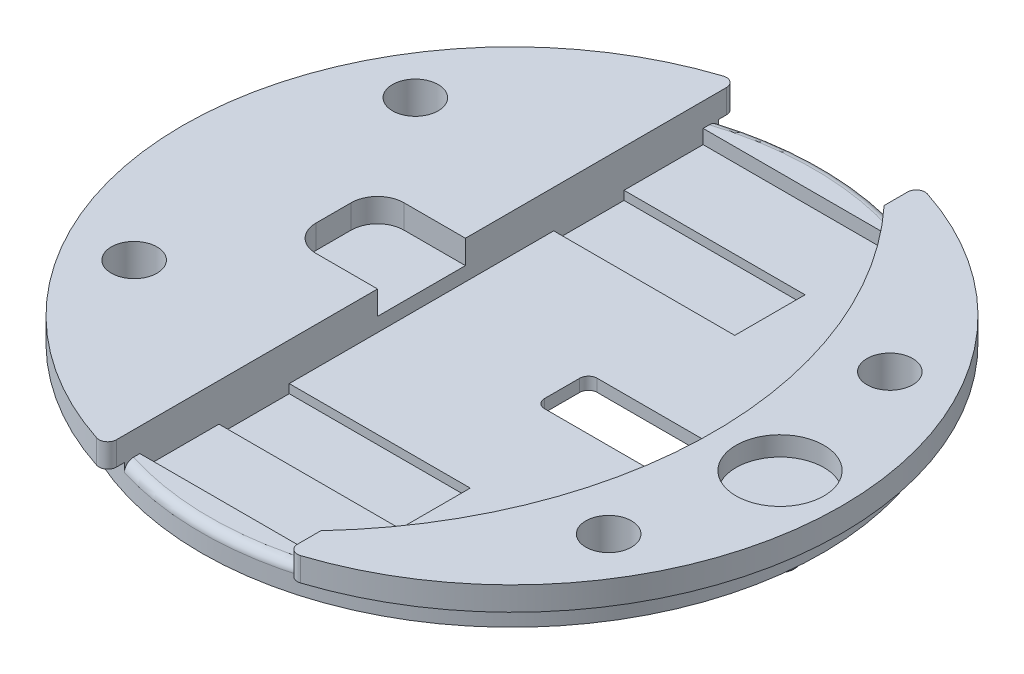
SolidWorks part; units mm, degrees
ref_plane "Front Plane" through (0, 0, 0) normal (0, 0, 1) x (1, 0, 0)
ref_plane "Top Plane" through (0, 0, 0) normal (0, 1, 0) x (1, 0, 0)
ref_plane "Right Plane" through (0, 0, 0) normal (1, 0, 0) x (0, 0, -1)
sketch "Sketch1" plane through (0, 0, 0) normal (0, 1, 0) x (1, 0, 0)
  line L1 (5.7, 3) -> (19.7, 3)
  line L2 (5.7, 3) -> (5.7, -3)
  line L3 (5.7, -3) -> (19.7, -3)
  line L4 (19.7, 3) -> (19.7, -3)
  line L5 (6.35, 2.54) -> (19.05, 2.54) construction
  line L6 (6.35, 2.54) -> (6.35, -2.54) construction
  line L7 (6.35, -2.54) -> (19.05, -2.54) construction
  line L8 (19.05, 2.54) -> (19.05, -2.54) construction
  line L9 (-27, 16) -> (27, 16) construction
  line L10 (-27, 16) -> (-27, -16) construction
  line L11 (-27, -16) -> (27, -16) construction
  line L12 (27, 16) -> (27, -16) construction
  circle A0 centre (0, 0) radius 35.35
  circle A1 centre (27, 16) radius 2.6
  circle A2 centre (-27, 16) radius 2.6
  circle A3 centre (-27, -16) radius 2.6
  circle A4 centre (27, -16) radius 2.6
  point P7 (5.7, 0)
  point P12 (12.7, -2.54)
  point P13 (12.7, -3)
  point P14 (6.35, 0)
  point P27 (0, 16)
  point P28 (27, 0)
  dimension "D1" = 70.7
  dimension "D7" = 5.2
  dimension "D8" = 5.2
  dimension "D9" = 5.2
  dimension "D10" = 5.2
  dimension "D2" = 6
  dimension "D3" = 14
  dimension "D4" = 5.08
  dimension "D5" = 12.7
  dimension "D6" = 6.35
  dimension "D11" = 54
  dimension "D12" = 32
extrude "Boss-Extrude1" add sketch "Sketch1" along normal blind 1.4
fillet "Fillet1" radius 1 4 edges at (5.7, 0.7, -3) (5.7, 0.7, 3) (19.7, 0.7, 3) (19.7, 0.7, -3)
sketch "Sketch3" plane through (0, 1.4, 0) normal (0, 1, 0) x (1, 0, 0)
  line L1 (-10.3, 32.05) -> (10.3, 32.05)
  line L2 (-10.3, 32.05) -> (-10.3, -32.05)
  line L3 (-10.3, -32.05) -> (10.3, -32.05)
  circle A0 centre (27, 16) radius 2.6 construction
  circle A1 centre (27, -16) radius 2.6 construction
  circle A2 centre (-27, -16) radius 2.6 construction
  circle A3 centre (-27, 16) radius 2.6 construction
  circle A4 centre (0, 0) radius 35.35 construction
  circle A5 centre (27, 16) radius 2.6
  circle A6 centre (27, -16) radius 2.6
  circle A7 centre (-27, -16) radius 2.6
  circle A8 centre (-27, 16) radius 2.6
  circle A9 centre (0, 0) radius 35.35
  arc A10 (10.3, -32.05) -> (10.3, 32.05) centre (-24.0773, 0) ccw
  point P20 (0, 32.05)
  point P23 (-10.3, 0)
  dimension "D3" = 47
  dimension "D1" = 20.6
  dimension "D2" = 64.1
extrude "Boss-Extrude3" add sketch "Sketch3" along normal blind 1.6
sketch "Sketch4" plane through (0, 3, 0) normal (0, 1, 0) x (1, 0, 0)
  line L0 (-10.3, 36.0577) -> (-10.3, 5)
  line L1 (-10.3, 32.05) -> (-10.3, -32.05) construction
  line L2 (10.3, 32.05) -> (10.3, 36.0577)
  line L3 (10.3, -32.05) -> (10.3, -36.0577)
  line L4 (-10.3, -5) -> (-10.3, -36.0577)
  line L5 (-10.3, -5) -> (-20.3, -5)
  line L7 (-10.3, 5) -> (-20.3, 5)
  line L8 (-20.3, -5) -> (-20.3, 5)
  arc A0 (10.3, -32.05) -> (10.3, 32.05) centre (-24.0773, 0) ccw construction
  arc A1 (10.3, -36.0577) -> (10.3, 36.0577) centre (0, 0) ccw
  arc A3 (10.3, -32.05) -> (10.3, 32.05) centre (-24.0773, 0) ccw
  circle A4 centre (-27, 16) radius 2.6 construction
  circle A5 centre (-27, -16) radius 2.6 construction
  circle A6 centre (27, -16) radius 2.6 construction
  circle A7 centre (27, 16) radius 2.6 construction
  circle A8 centre (-27, 16) radius 2.6
  circle A9 centre (-27, -16) radius 2.6
  circle A10 centre (27, -16) radius 2.6
  circle A11 centre (27, 16) radius 2.6
  arc A12 (-10.3, 36.0577) -> (-10.3, -36.0577) centre (0, 0) ccw
  point P27 (-20.3, 0)
  dimension "D1" = 75
  dimension "D2" = 10
  dimension "D3" = 10
extrude "Boss-Extrude4" add sketch "Sketch4" along normal blind 2.7
sketch "Sketch5" plane through (0, 5.7, 0) normal (0, 1, 0) x (1, 0, 0)
  circle A0 centre (30.5, 0) radius 5
  dimension "D2" = 10
  dimension "D1" = 30.5
extrude "Cut-Extrude1" cut sketch "Sketch5" against normal blind 2.2
sketch "Sketch7" plane through (0, 1.4, 0) normal (0, 1, 0) x (1, 0, 0)
  line L0 (-10.3, 32.05) -> (-10.3, -32.05) construction
  line L1 (-10.3, -23.05) -> (10.3, -23.05)
  line L2 (-10.3, -23.05) -> (-10.3, -15.05)
  line L3 (-10.3, -15.05) -> (10.3, -15.05)
  line L4 (10.3, -23.05) -> (10.3, -15.05)
  line L5 (-10.3, -36.0577) -> (-10.3, -5) construction
  line L6 (-10.3, 15.05) -> (10.3, 15.05)
  line L7 (-10.3, 15.05) -> (-10.3, 23.05)
  line L8 (-10.3, 23.05) -> (10.3, 23.05)
  line L9 (10.3, 15.05) -> (10.3, 23.05)
  line L10 (10.3, 36.0577) -> (10.3, 32.05) construction
  line L11 (10.3, -32.05) -> (10.3, -36.0577) construction
  line L12 (10.3, 32.05) -> (-10.3, 32.05) construction
  line L13 (-10.3, -32.05) -> (10.3, -32.05) construction
  dimension "D1" = 8
  dimension "D2" = 8
  dimension "D3" = 9
  dimension "D4" = 9
extrude "Cut-Extrude3" cut sketch "Sketch7" against normal blind 1
sketch "Sketch8" plane through (0, 0, 0) normal (0, -1, 0) x (1, 0, 0)
  circle A0 centre (30.5, 0) radius 1.9
  dimension "D2" = 3.8
  dimension "D1" = 30.5
extrude "Boss-Extrude6" add sketch "Sketch8" along normal blind 3.5
fillet "Fillet2" radius 1 7 edges at (10.3, 4.35, 36.0577) (0, 3, 35.35) (-10.3, 4.35, 36.0577) (-10.3, 4.35, -36.0577) (0, 3, -35.35) (10.3, 4.35, -36.0577) (30.5, -3.5, -1.9)
sketch "Sketch9" plane through (0, 3, 0) normal (0, -1, 0) x (1, 0, 0)
  line L0 (-10.3, -34.7068) -> (-10.3, -33.8162) construction
  line L1 (-10.3, 33.8162) -> (-10.3, 34.7068) construction
  line L2 (10.3, -33.8162) -> (10.3, -34.7068) construction
  line L3 (10.3, 34.7068) -> (10.3, 33.8162) construction
  line L4 (-10.3, -34.7068) -> (-10.3, -33.8162)
  line L5 (-10.3, 33.8162) -> (-10.3, 34.7068)
  line L6 (10.3, -33.8162) -> (10.3, -34.7068)
  line L7 (10.3, 34.7068) -> (10.3, 33.8162)
  arc A0 (-11.6096, 35.6576) -> (-11.6096, -35.6576) centre (0, 0) ccw construction
  arc A1 (-11.6096, -35.6576) -> (-10.3, -34.7068) centre (-11.3, -34.7068) ccw construction
  arc A2 (-10.3, 33.8162) -> (-10.3, -33.8162) centre (0, 0) ccw construction
  arc A3 (-10.3, 34.7068) -> (-11.6096, 35.6576) centre (-11.3, 34.7068) ccw construction
  arc A4 (10.3, -34.7068) -> (11.6096, -35.6576) centre (11.3, -34.7068) ccw construction
  arc A5 (11.6096, -35.6576) -> (11.6096, 35.6576) centre (0, 0) ccw construction
  arc A6 (11.6096, 35.6576) -> (10.3, 34.7068) centre (11.3, 34.7068) ccw construction
  arc A7 (10.3, -33.8162) -> (10.3, 33.8162) centre (0, 0) ccw construction
  arc A8 (-11.6096, 35.6576) -> (-11.6096, -35.6576) centre (0, 0) ccw
  arc A9 (-11.6096, -35.6576) -> (-10.3, -34.7068) centre (-11.3, -34.7068) ccw
  arc A10 (-10.3, 33.8162) -> (-10.3, -33.8162) centre (0, 0) ccw
  arc A11 (-10.3, 34.7068) -> (-11.6096, 35.6576) centre (-11.3, 34.7068) ccw
  arc A12 (10.3, -34.7068) -> (11.6096, -35.6576) centre (11.3, -34.7068) ccw
  arc A13 (11.6096, -35.6576) -> (11.6096, 35.6576) centre (0, 0) ccw
  arc A14 (11.6096, 35.6576) -> (10.3, 34.7068) centre (11.3, 34.7068) ccw
  arc A15 (10.3, -33.8162) -> (10.3, 33.8162) centre (0, 0) ccw
fillet "Fillet3" radius 3 2 edges at (-20.3, 4.35, 5) (-20.3, 4.35, -5)
